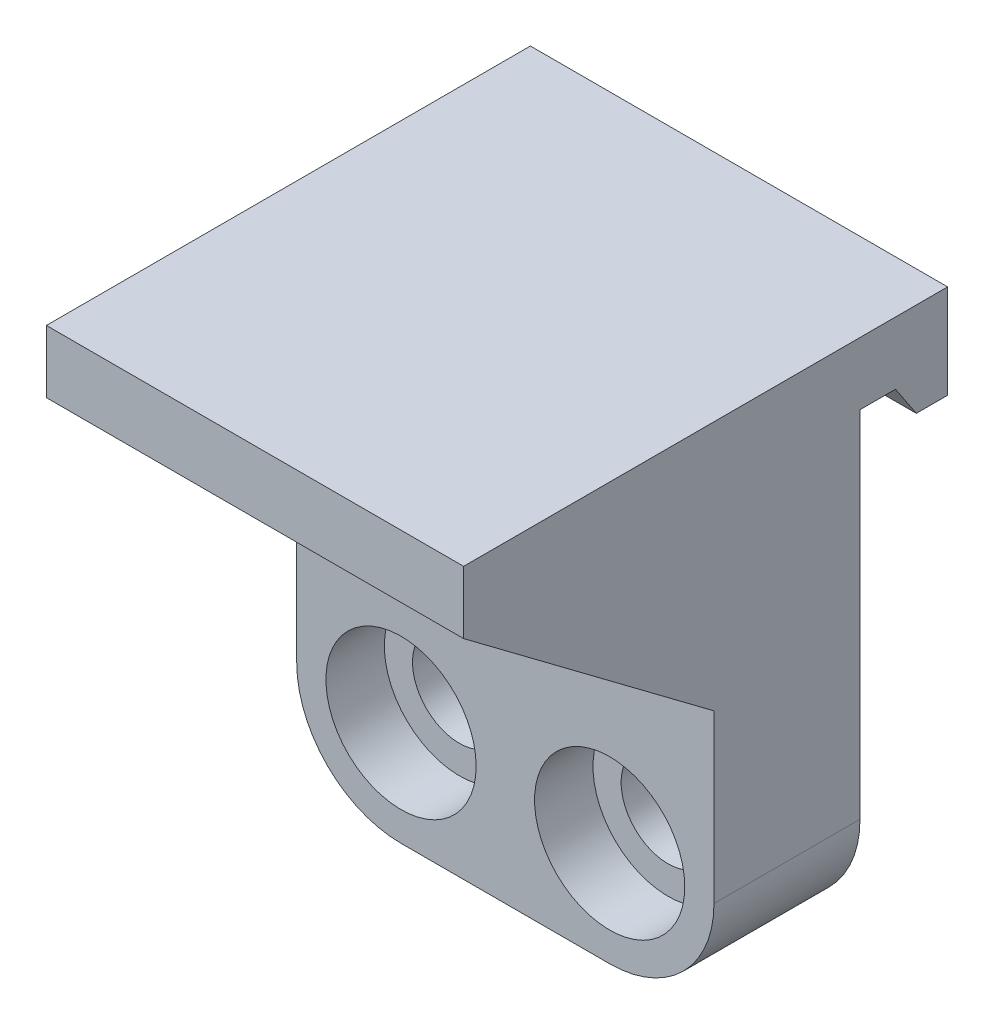
SolidWorks part; units mm, degrees
ref_plane "Front Plane" through (0, 0, 0) normal (0, 0, 1) x (1, 0, 0)
ref_plane "Top Plane" through (0, 0, 0) normal (0, 1, 0) x (1, 0, 0)
ref_plane "Right Plane" through (0, 0, 0) normal (1, 0, 0) x (0, 0, -1)
sketch "Sketch1" plane through (0, 0, 0) normal (0, 0, 1) x (1, 0, 0)
  line L1 (-10, 12.5) -> (10, 12.5)
  line L2 (-10, 12.5) -> (-10, -12.5)
  line L3 (-10, -12.5) -> (10, -12.5)
  line L4 (10, 12.5) -> (10, -12.5)
  line L5 (-10, 12.5) -> (10, -12.5) construction
  line L6 (-10, -12.5) -> (10, 12.5) construction
  circle A0 centre (-5, -7.5) radius 2.25
  circle A1 centre (5, -7.5) radius 2.25
  point P0 (0, 0)
  dimension "D3" = 20
  dimension "D4" = 20
  dimension "D5" = 10
  dimension "D6" = 5
  dimension "D7" = 4.5
  dimension "D8" = 4.5
  dimension "D1" = 25
  dimension "D2" = 20
extrude "Boss-Extrude1" add sketch "Sketch1" along normal blind 7
sketch "Sketch2" plane through (0, 0, 7) normal (0, 0, 1) x (1, 0, 0)
  circle A0 centre (-5, -7.5) radius 3.6
  circle A1 centre (5, -7.5) radius 3.6
  dimension "D1" = 7.2
  dimension "D2" = 7.2
extrude "Cut-Extrude1" cut sketch "Sketch2" against normal blind 2.8
fillet "Fillet2" radius 5 2 edges at (10, -12.5, 3.5) (-10, -12.5, 3.5)
sketch "Sketch3" plane through (-10, 0, 0) normal (-1, 0, 0) x (0, 0, 1)
  line L2 (7, 12.5) -> (7, -7.5) construction
  line L3 (7, 0.5) -> (7, 12.5)
  line L4 (7, 12.5) -> (19, 12.5)
  line L5 (19, 12.5) -> (19, 9.5)
  line L6 (19, 9.5) -> (7, 0.5)
  dimension "D1" = 12
  dimension "D2" = 12
  dimension "D3" = 3
  dimension "D4" = 15
extrude "Boss-Extrude2" add sketch "Sketch3" against normal through all
sketch "Sketch4" plane through (-10, 0, 0) normal (-1, 0, 0) x (0, 0, 1)
  line L0 (-1.7, 12.5) -> (-4.2, 12.5)
  line L1 (0, 12.5) -> (-1.7, 12.5)
  line L2 (0, 12.5) -> (0, 9.5)
  line L3 (0, 9.5) -> (-1.7, 9.5)
  line L4 (-1.7, 12.5) -> (-1.7, 9.5)
  line L5 (-4.2, 12.5) -> (-4.2, 8)
  line L6 (-4.2, 8) -> (-2.7, 8)
  line L7 (-2.7, 8) -> (-1.7, 9.5)
  line M3 (0, 12.5) -> (0, -7.5)
  dimension "D1" = 1.7
  dimension "D2" = 3
  dimension "D3" = 2.5
  dimension "D4" = 4.5
  dimension "D5" = 1.5
extrude "Boss-Extrude3" add sketch "Sketch4" against normal through all contours L6 L7 L4 L0 L5 | L1 L4 L3 M3 region at (-10, 10.375, -3.0155) region at (-10, 11, -0.85)
